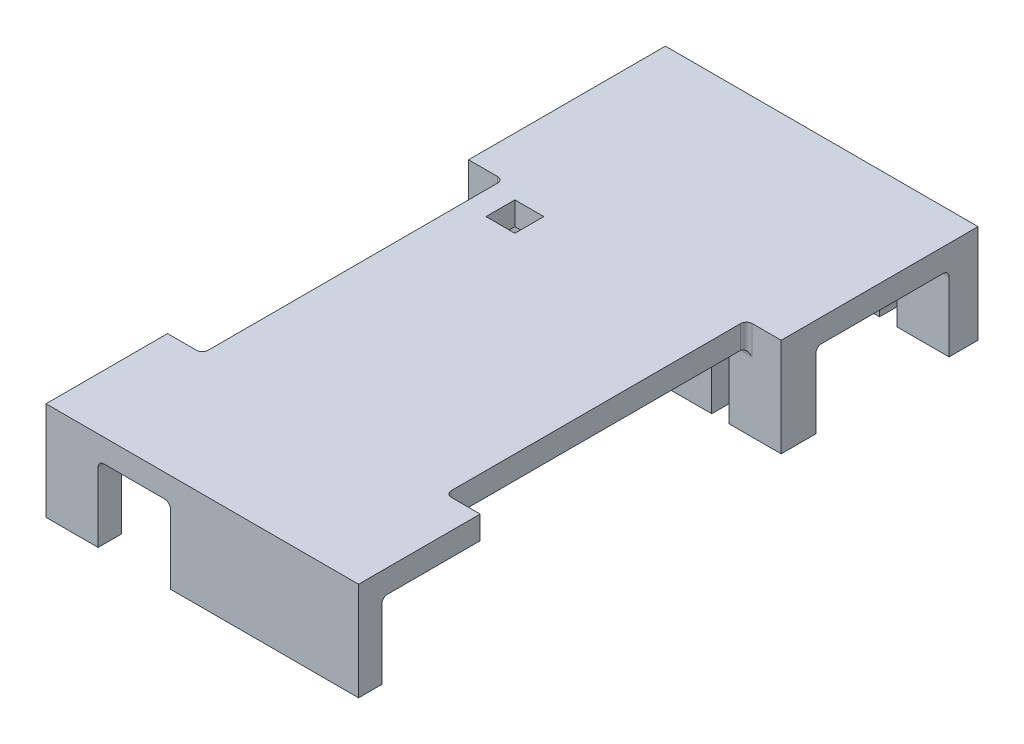
SolidWorks part; units mm, degrees
ref_plane "Front Plane" through (0, 0, 0) normal (0, 0, 1) x (1, 0, 0)
ref_plane "Top Plane" through (0, 0, 0) normal (0, 1, 0) x (1, 0, 0)
ref_plane "Right Plane" through (0, 0, 0) normal (1, 0, 0) x (0, 0, -1)
sketch "Sketch1" plane through (0, 0, 0) normal (0, 1, 0) x (1, 0, 0)
  line L1 (0, 0) -> (54, 0)
  line L2 (0, 0) -> (0, 69)
  line L3 (0, 69) -> (54, 69)
  line L4 (54, 0) -> (54, 69)
  line L5 (0, 0) -> (9, 0)
  line L6 (0, 0) -> (0, -4)
  line L7 (0, -4) -> (9, -4)
  line L8 (9, 0) -> (9, -4)
  line L9 (21.5, 0) -> (54, 0)
  line L10 (21.5, 0) -> (21.5, -4)
  line L11 (21.5, -4) -> (54, -4)
  line L12 (54, 0) -> (54, -4)
  line L13 (0, 69) -> (54, 69)
  line L14 (0, 69) -> (0, 73)
  line L15 (0, 73) -> (54, 73)
  line L16 (54, 69) -> (54, 73)
  dimension "D1" = 69
  dimension "D2" = 54
  dimension "D3" = 4
  dimension "D4" = 4
  dimension "D5" = 4
  dimension "D6" = 9
  dimension "D7" = 12.5
extrude "Boss-Extrude1" add sketch "Sketch1" along normal blind 13 contours L12 L1 L10 L11 | L8 L1 L6 L7 | L3 L16 L15 L14 region at (4.5, 0, 2) region at (27, 0, -71) region at (37.75, 0, 2)
sketch "Sketch2" plane through (0, 13, 0) normal (0, 1, 0) x (1, 0, 0)
  line L1 (0, -4) -> (54, -4)
  line L2 (0, -4) -> (0, 73)
  line L3 (0, 73) -> (54, 73)
  line L4 (54, -4) -> (54, 73)
  line L5 (0, 69) -> (6, 69)
  line L6 (0, 69) -> (0, 17)
  line L7 (0, 17) -> (6, 17)
  line L8 (6, 69) -> (6, 17)
  line L9 (54, 69) -> (48, 69)
  line L10 (54, 69) -> (54, 17)
  line L11 (54, 17) -> (48, 17)
  line L12 (48, 69) -> (48, 17)
  line M12 (9, -4) -> (9, 0)
  line M13 (9, 0) -> (0, 0)
  line M14 (0, 0) -> (0, -4)
  line M15 (0, -4) -> (9, -4)
  dimension "D1" = 6
  dimension "D2" = 52
  dimension "D3" = 52
  dimension "D4" = 6
extrude "Boss-Extrude2" add sketch "Sketch2" along normal blind 4 contours L12 L9 L4 L3 L2 L5 L8 L7 L1 L11 M13 M12 | M15 M12 M13 M14 region at (4.5, 13, 2) region at (27.2316, 13, -33.3593)
sketch "Sketch4" plane through (0, 0, -73) normal (0, 0, -1) x (-1, 0, 0)
  line L1 (-54, 0) -> (0, 0)
  line L2 (-54, 0) -> (-54, 17)
  line L3 (-54, 17) -> (0, 17)
  line L4 (0, 0) -> (0, 17)
extrude "Boss-Extrude3" add sketch "Sketch4" along normal blind 2
sketch "Sketch6" plane through (0, 0, -75) normal (0, 0, -1) x (-1, 0, 0)
  line L0 (-54, 0) -> (0, 0) construction
  line L1 (-45, 0) -> (-42, 0)
  line L2 (-45, 0) -> (-45, 13)
  line L3 (-45, 13) -> (-42, 13)
  line L4 (-42, 0) -> (-42, 13)
  line L5 (-54, 17) -> (-54, 0) construction
  point P8 (-43.5, 13)
  dimension "D1" = 3
  dimension "D2" = 9
  dimension "D3" = 13
extrude "Cut-Extrude1" cut sketch "Sketch6" against normal blind 12
sketch "Sketch7" plane through (0, 0, -75) normal (0, 0, -1) x (-1, 0, 0)
  line L0 (0, 0) -> (0, 17) construction
  line L1 (-54, 17) -> (0, 17)
  line L2 (-54, 17) -> (-54, 13)
  line L3 (-54, 13) -> (0, 13)
  line L4 (0, 17) -> (0, 13)
extrude "Boss-Extrude4" add sketch "Sketch7" along normal blind 28
sketch "Sketch9" plane through (0, 13, 0) normal (0, -1, 0) x (-1, 0, 0)
  line L1 (-54, 103) -> (-45, 103)
  line L2 (-54, 103) -> (-54, 98)
  line L3 (-54, 98) -> (-45, 98)
  line L4 (-45, 103) -> (-45, 98)
  line L5 (0, 103) -> (-42, 103)
  line L6 (0, 103) -> (0, 98)
  line L7 (0, 98) -> (-42, 98)
  line L8 (-42, 103) -> (-42, 98)
  dimension "D1" = 5
  dimension "D2" = 5
  dimension "D3" = 9
  dimension "D4" = 3
extrude "Boss-Extrude5" add sketch "Sketch9" along normal blind 13
sketch "Sketch10" plane through (0, 17, 0) normal (0, 1, 0) x (1, 0, 0)
  line L0 (0, 69) -> (0, 103) construction
  line L1 (10, 67) -> (15, 67)
  line L2 (10, 67) -> (10, 62)
  line L3 (10, 62) -> (15, 62)
  line L4 (15, 67) -> (15, 62)
  line L5 (0, 103) -> (54, 103) construction
  dimension "D1" = 5
  dimension "D2" = 5
  dimension "D3" = 10
  dimension "D4" = 36
extrude "Cut-Extrude2" cut sketch "Sketch10" against normal blind 13
sketch "Sketch11" plane through (0, 0, 0) normal (0, -1, 0) x (-1, 0, 0)
  line L0 (-42, 75) -> (0, 75) construction
  line L1 (-32, 75) -> (-26, 75)
  line L2 (-32, 75) -> (-32, 69)
  line L3 (-32, 69) -> (-26, 69)
  line L4 (-26, 75) -> (-26, 69)
  line L5 (0, 69) -> (-42, 69) construction
  line L6 (-42, 69) -> (-42, 75) construction
  dimension "D1" = 10
  dimension "D2" = 6
extrude "Cut-Extrude3" cut sketch "Sketch11" against normal blind 13
fillet "Fillet1" radius 1 10 edges at (21, 13, -98) (49.5, 13, -98) (49.5, 13, -75) (37, 13, -75) (13, 13, -75) (37.75, 13, 0) (4.5, 13, 0) (16, 13, -69) (37, 13, -69) (46.5, 13, -69)
sketch "Sketch12" plane through (0, 13, 0) normal (0, -1, 0) x (-1, 0, 0)
  line L0 (0, 97) -> (0, 76) construction
  line L1 (0, 88) -> (-5, 88)
  line L2 (0, 88) -> (0, 103)
  line L3 (0, 103) -> (-5, 103)
  line L4 (-5, 88) -> (-5, 103)
  line L5 (0, 103) -> (-42, 103) construction
  dimension "D1" = 5
  dimension "D2" = 15
extrude "Boss-Extrude6" add sketch "Sketch12" along normal blind 13
fillet "Fillet2" radius 1 3 edges at (5, 6, -98) (5, 12.7071, -97.7071) (5, 13, -92.5)
fillet "Fillet3" radius 1 1 edges at (3, 13, -88)
sketch "Sketch13" plane through (0, 0, 0) normal (0, -1, 0) x (-1, 0, 0)
  line L0 (0, 103) -> (-42, 103) construction
  line L1 (-24, 103) -> (-20, 103)
  line L2 (-24, 103) -> (-24, 98)
  line L4 (-20, 103) -> (-20, 98)
  line L5 (-42, 98) -> (-6, 98) construction
  line L6 (-54, 103) -> (-54, 98) construction
  line L7 (0, 88) -> (0, 103) construction
  line L10 (-24, 98) -> (-24, 93.2819)
  line L11 (-24, 93.2819) -> (-20, 93.2819)
  line L12 (-20, 98) -> (-20, 93.2819)
  dimension "D1" = 30
  dimension "D2" = 20
extrude "Cut-Extrude4" cut sketch "Sketch13" against normal blind 13
fillet "Fillet4" radius 1 2 edges at (20, 13, -100) (24, 13, -100)
fillet "Fillet5" radius 1 8 edges at (9, 13, 1.5) (21.5, 13, 1.5) (26, 13, -72) (32, 13, -72) (42, 13, -72) (45, 13, -72) (42, 13, -100) (45, 13, -100)
fillet "Fillet6" radius 1 4 edges at (6, 15, -17) (48, 15, -17) (48, 14.5, -69) (6, 14.5, -69)
